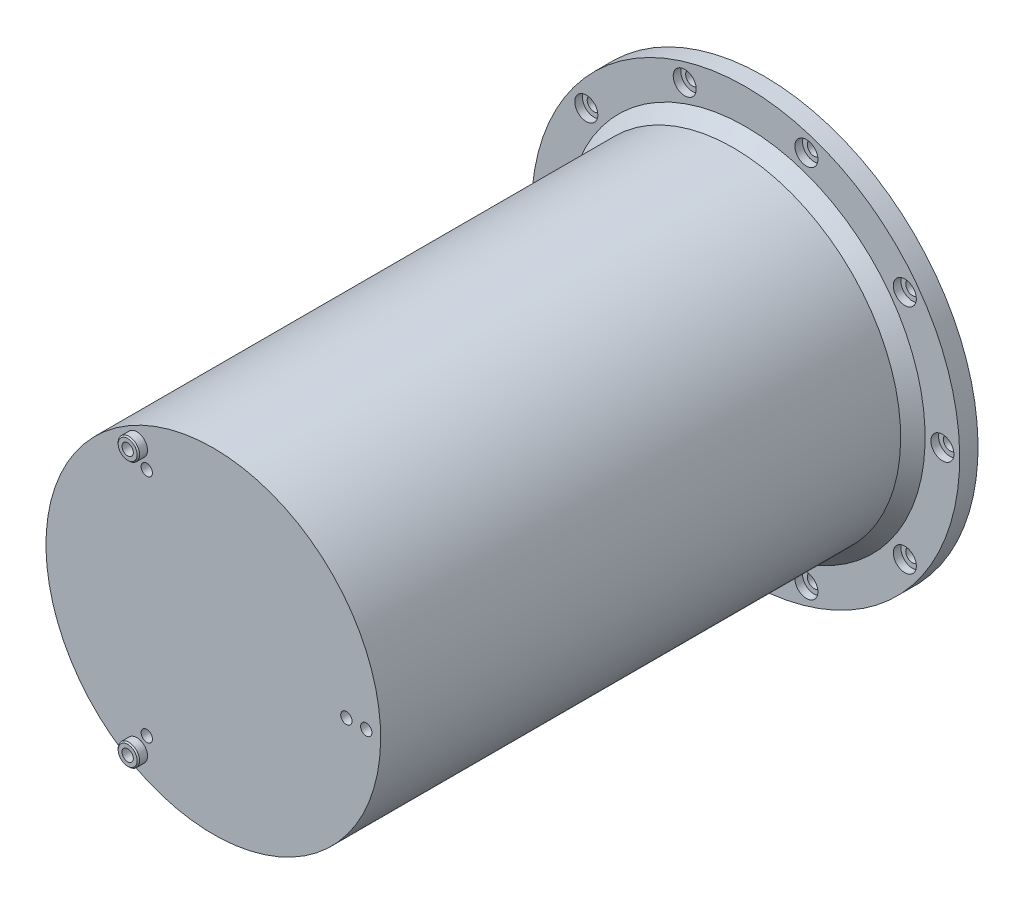
SolidWorks part; units mm, degrees
ref_plane "Piano frontale" through (0, 0, 0) normal (0, 0, 1) x (1, 0, 0)
ref_plane "Piano superiore" through (0, 0, 0) normal (0, 1, 0) x (1, 0, 0)
ref_plane "Piano destro" through (0, 0, 0) normal (1, 0, 0) x (0, 0, -1)
sketch "Schizzo1" plane through (0, 0, -132.2078) normal (0, 0, -1) x (-1, 0, 0)
  circle A14 centre (214.1711, -331.6849) radius 273.5326
  arc A15 (311.7735, -587.2115) -> (380.5507, -548.7976) centre (214.1711, -331.6849) ccw construction
  arc A16 (-35.8289, -322.4349) -> (-35.8289, -340.9349) centre (-35.8289, -331.6849) ccw construction
  arc A17 (-35.8289, -340.9349) -> (-35.8289, -322.4349) centre (-35.8289, -331.6849) ccw construction
  arc A18 (-3.3289, -340.9349) -> (-3.3289, -322.4349) centre (-3.3289, -331.6849) ccw construction
  arc A19 (-3.3289, -322.4349) -> (-3.3289, -340.9349) centre (-3.3289, -331.6849) ccw construction
  arc A20 (322.9211, -134.0744) -> (322.9211, -152.5744) centre (322.9211, -143.3244) ccw construction
  arc A21 (322.9211, -152.5744) -> (322.9211, -134.0744) centre (322.9211, -143.3244) ccw construction
  arc A22 (339.1711, -124.4286) -> (339.1711, -105.9286) centre (339.1711, -115.1786) ccw construction
  arc A23 (339.1711, -105.9286) -> (339.1711, -124.4286) centre (339.1711, -115.1786) ccw construction
  arc A24 (322.9211, -529.2954) -> (322.9211, -510.7954) centre (322.9211, -520.0454) ccw construction
  arc A25 (322.9211, -510.7954) -> (322.9211, -529.2954) centre (322.9211, -520.0454) ccw construction
  arc A26 (339.1711, -557.4413) -> (339.1711, -538.9413) centre (339.1711, -548.1913) ccw construction
  arc A27 (339.1711, -538.9413) -> (339.1711, -557.4413) centre (339.1711, -548.1913) ccw construction
  arc A28 (-35.8289, -322.4349) -> (-35.8289, -340.9349) centre (-35.8289, -331.6849) ccw
  arc A29 (-35.8289, -340.9349) -> (-35.8289, -322.4349) centre (-35.8289, -331.6849) ccw
  arc A30 (-3.3289, -340.9349) -> (-3.3289, -322.4349) centre (-3.3289, -331.6849) ccw
  arc A31 (-3.3289, -322.4349) -> (-3.3289, -340.9349) centre (-3.3289, -331.6849) ccw
  arc A32 (322.9211, -134.0744) -> (322.9211, -152.5744) centre (322.9211, -143.3244) ccw
  arc A33 (322.9211, -152.5744) -> (322.9211, -134.0744) centre (322.9211, -143.3244) ccw
  arc A34 (339.1711, -124.4286) -> (339.1711, -105.9286) centre (339.1711, -115.1786) ccw
  arc A35 (339.1711, -105.9286) -> (339.1711, -124.4286) centre (339.1711, -115.1786) ccw
  arc A36 (322.9211, -529.2954) -> (322.9211, -510.7954) centre (322.9211, -520.0454) ccw
  arc A37 (322.9211, -510.7954) -> (322.9211, -529.2954) centre (322.9211, -520.0454) ccw
  arc A38 (339.1711, -557.4413) -> (339.1711, -538.9413) centre (339.1711, -548.1913) ccw
  arc A39 (339.1711, -538.9413) -> (339.1711, -557.4413) centre (339.1711, -548.1913) ccw
extrude "Estrusione-Estrusione1" add sketch "Schizzo1" along normal blind 15
sketch "Schizzo5" plane through (0, 0, -147.2078) normal (0, 0, -1) x (-1, 0, 0)
  circle A0 centre (214.1711, -331.6849) radius 273.5326 construction
  circle A1 centre (214.1711, -331.6849) radius 273.5326
extrude "Estrusione-Estrusione4" add sketch "Schizzo5" along normal blind 885
sketch "Schizzo6" plane through (0, 0, -1032.2078) normal (0, 0, -1) x (-1, 0, 0)
  circle A0 centre (214.1711, -331.6849) radius 350
  dimension "D1" = 700
extrude "Estrusione-Estrusione5" add sketch "Schizzo6" against normal blind 30
chamfer "Smusso2" distance 20 angle 45 1 edges at (-214.1711, -58.1523, -1002.2078)
sketch "Schizzo7" plane through (0, 0, -1002.2078) normal (0, 0, 1) x (1, 0, 0)
  line L0 (135.8289, -331.6849) -> (107.5952, -331.6849) construction
  line L1 (107.5952, -331.6849) -> (79.3615, -331.6849) construction
  circle A0 centre (-214.1711, -331.6849) radius 321.7663
  circle A1 centre (-214.1711, -331.6849) radius 350 construction
  circle A2 centre (-214.1711, -331.6849) radius 293.5326 construction
  point P11 (107.5952, -331.6849)
hole_wizard "Foro lamato per Bullone M20 a testa esagonale-1" positions "Schizzo3D1" profile "Schizzo9" counterbore size "M20" standard "ISO" end condition through all
sketch3d "Schizzo3D1"
  point P0 (107.5952, -331.6849, -1002.2078)
sketch "Schizzo9" plane through (107.5952, -331.6849, -1002.2078) normal (1, 0, 0) x (0, -1, 0)
  line L0 (0, 0) -> (0, 30)
  line L1 (0, 30) -> (11, 30)
  line L3 (11, 30) -> (11, 12.5)
  line L4 (11, 12.5) -> (18.8205, 12.5)
  line L5 (18.8205, 12.5) -> (18.8205, 0)
  line L7 (18.8205, 0) -> (0, 0)
  line L11 (0, -6.35) -> (0, 107.95) construction
  dimension "Thru Hole Dia." = 22
  dimension "Thru Hole Depth" = 30
  dimension "C'Bore Dia." = 37.641
  dimension "C'Bore Depth" = 12.5
pattern_circular "RipetizioneCircolare1" count 10 every 36 about axis through (-214.1711, -331.6849, -132.2078) along (0, 0, -1) of "Foro lamato per Bullone M20 a testa esagonale-1"
sketch "Schizzo10" plane through (0, 0, -132.2078) normal (0, 0, 1) x (1, 0, 0)
  arc A0 (-339.1711, -132.6786) -> (-339.1711, -97.6786) centre (-339.1711, -115.1786) ccw construction
  arc A1 (-339.1711, -97.6786) -> (-339.1711, -132.6786) centre (-339.1711, -115.1786) ccw construction
  arc A2 (-339.1711, -565.6913) -> (-339.1711, -530.6913) centre (-339.1711, -548.1913) ccw construction
  arc A3 (-339.1711, -530.6913) -> (-339.1711, -565.6913) centre (-339.1711, -548.1913) ccw construction
  arc A4 (-339.1711, -132.6786) -> (-339.1711, -97.6786) centre (-339.1711, -115.1786) ccw
  arc A5 (-339.1711, -97.6786) -> (-339.1711, -132.6786) centre (-339.1711, -115.1786) ccw
  arc A6 (-339.1711, -565.6913) -> (-339.1711, -530.6913) centre (-339.1711, -548.1913) ccw
  arc A7 (-339.1711, -530.6913) -> (-339.1711, -565.6913) centre (-339.1711, -548.1913) ccw
  circle A8 centre (-339.1711, -548.1913) radius 9.25 construction
  circle A9 centre (-339.1711, -115.1786) radius 9.25 construction
  circle A10 centre (-339.1711, -548.1913) radius 9.25
  circle A11 centre (-339.1711, -115.1786) radius 9.25
extrude "Estrusione-Estrusione6" add sketch "Schizzo10" along normal blind 15
chamfer "Smusso3" distance 2 angle 45 2 edges at (-321.6711, -115.1786, -117.2078) (-321.6711, -548.1913, -117.2078)
